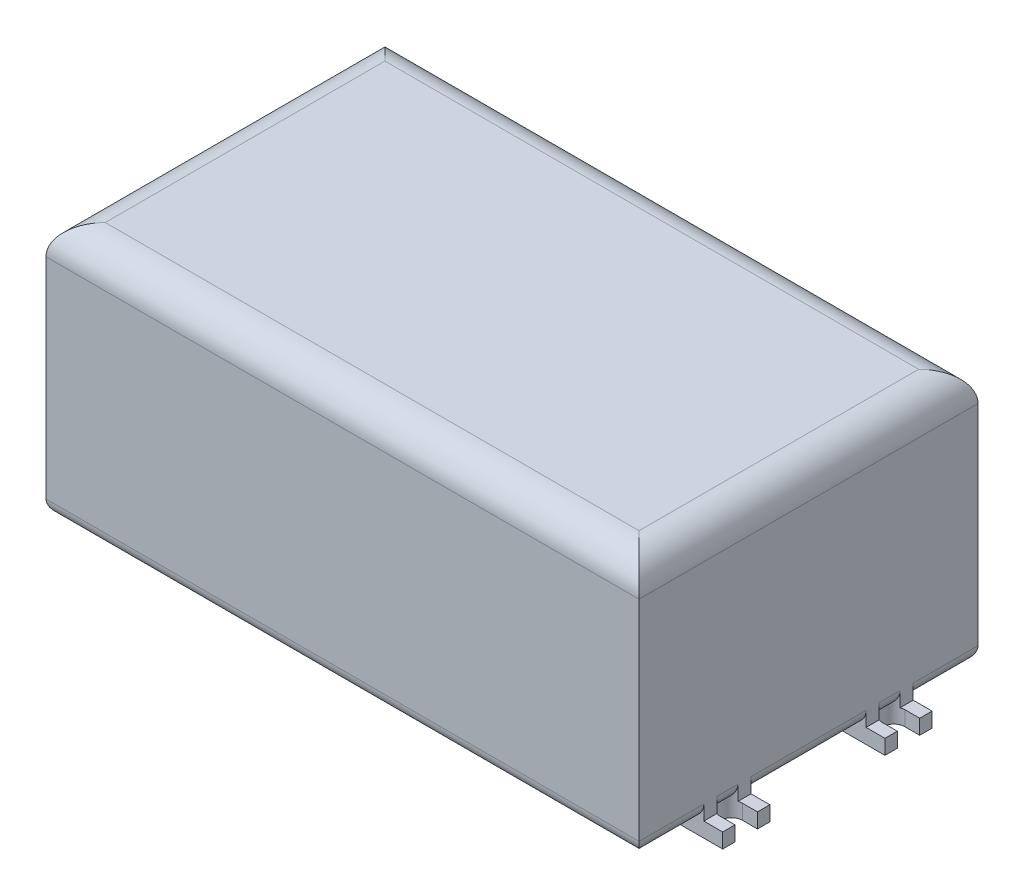
SolidWorks part; units mm, degrees
material "Custom Plastic"
ref_plane "Front Plane" through (0, 0, 0) normal (0, 0, 1) x (1, 0, 0)
ref_plane "Top Plane" through (0, 0, 0) normal (0, 1, 0) x (1, 0, 0)
ref_plane "Right Plane" through (0, 0, 0) normal (1, 0, 0) x (0, 0, -1)
sketch "Sketch1" plane through (0, 0, 0) normal (0, 1, 0) x (1, 0, 0)
  line L0 (106.36, 39.1183) -> (-106.36, 39.1183)
  line L1 (-106.36, 39.1183) -> (-106.36, 34.9483)
  line L2 (-106.36, 34.9483) -> (-101.36, 34.9483)
  line L5 (-106.36, 27.3883) -> (-101.36, 27.3883)
  line L6 (-106.36, 23.2183) -> (-106.36, 27.3883)
  line L8 (106.36, 23.2183) -> (106.36, 27.3883)
  line L9 (106.36, 27.3883) -> (101.36, 27.3883)
  line L10 (106.36, 34.9483) -> (101.36, 34.9483)
  line L11 (106.36, 39.1183) -> (106.36, 34.9483)
  line L12 (-8.6573, 23.2183) -> (-106.36, 23.2183)
  line L14 (8.6573, -15.5917) -> (8.6573, 23.2183)
  line L16 (-8.6573, -15.5917) -> (-8.6573, 23.2183)
  line L17 (8.6573, 23.2183) -> (106.36, 23.2183)
  line L18 (106.36, -15.5917) -> (8.6573, -15.5917)
  line L19 (106.36, -15.5917) -> (106.36, -19.7617)
  line L20 (106.36, -19.7617) -> (101.36, -19.7617)
  line L21 (106.36, -27.3217) -> (101.36, -27.3217)
  line L22 (106.36, -31.4917) -> (106.36, -27.3217)
  line L23 (106.36, -31.4917) -> (-106.36, -31.4917)
  line L24 (-106.36, -31.4917) -> (-106.36, -27.3217)
  line L25 (-106.36, -27.3217) -> (-101.36, -27.3217)
  line L26 (-106.36, -19.7617) -> (-101.36, -19.7617)
  line L27 (-106.36, -15.5917) -> (-106.36, -19.7617)
  line L29 (-8.6573, -15.5917) -> (-106.36, -15.5917)
  arc A0 (-101.36, 34.9483) -> (-101.36, 27.3883) centre (-101.36, 31.1683) cw
  arc A1 (101.36, 34.9483) -> (101.36, 27.3883) centre (101.36, 31.1683) ccw
  arc A2 (101.36, -27.3217) -> (101.36, -19.7617) centre (101.36, -23.5417) cw
  arc A3 (-101.36, -27.3217) -> (-101.36, -19.7617) centre (-101.36, -23.5417) ccw
  point P5 (0, 6.2533)
  dimension "D4" = 4.17
  dimension "D6" = 3.78
  dimension "D8" = 3.78
  dimension "D3" = 3.78
  dimension "D9" = 3.78
  dimension "D1" = 212.72
  dimension "D2" = 4.17
  dimension "D5" = 38.81
  dimension "D7" = 4.17
  dimension "D10" = 4.17
extrude "Boss-Extrude1" add sketch "Sketch1" along normal mid plane 5
sketch "Sketch2" plane through (0, 2.5, 0) normal (0, 1, 0) x (1, 0, 0)
  line L0 (-8.6573, 3.8133) -> (8.6573, 3.8133)
  line L1 (-8.6573, 23.2183) -> (-8.6573, -15.5917) construction
  line L2 (8.6573, -15.5917) -> (8.6573, 23.2183) construction
  line L4 (-100, -53.3367) -> (100, -53.3367)
  line L5 (-100, -53.3367) -> (-100, 60.9633)
  line L6 (-100, 60.9633) -> (100, 60.9633)
  line L7 (100, -53.3367) -> (100, 60.9633)
  line L8 (-100, -53.3367) -> (100, 60.9633) construction
  line L9 (-100, 60.9633) -> (100, -53.3367) construction
  point P6 (0, 3.8133)
  dimension "D1" = 114.3
  dimension "D2" = 200
extrude "Boss-Extrude3" add sketch "Sketch2" along normal blind 85.725 contours L5 L6 L7 L4
sketch "Sketch3" plane through (-100, 0, 0) normal (-1, 0, 0) x (0, 0, 1)
  line L0 (-60.9633, 45.3625) -> (53.3367, 45.3625)
  line L1 (-60.9633, 88.225) -> (-60.9633, 2.5) construction
  line L2 (53.3367, 88.225) -> (53.3367, 2.5) construction
  line L3 (-3.8133, 88.225) -> (-3.8133, 2.5)
  line L4 (53.3367, 88.225) -> (-60.9633, 88.225) construction
  line L5 (-23.2183, 2.5) -> (15.5917, 2.5) construction
  line L6 (-16.2033, 41.9216) -> (6.1167, 41.9216)
  line L7 (-36.2033, 35.3625) -> (-16.2033, 35.3625)
  line L8 (-36.2033, 35.3625) -> (-36.2033, 55.3625)
  line L9 (-36.2033, 55.3625) -> (-16.2033, 55.3625)
  line L11 (-36.2033, 35.3625) -> (-16.2033, 55.3625) construction
  line L12 (-36.2033, 55.3625) -> (-16.2033, 35.3625) construction
  line L13 (6.1167, 35.3625) -> (26.1167, 35.3625)
  line L15 (6.1167, 55.3625) -> (26.1167, 55.3625)
  line L16 (26.1167, 35.3625) -> (26.1167, 55.3625)
  line L17 (6.1167, 35.3625) -> (26.1167, 55.3625) construction
  line L18 (6.1167, 55.3625) -> (26.1167, 35.3625) construction
  line L19 (-16.2033, 41.9216) -> (-16.2033, 35.3625)
  line L20 (6.1167, 41.9216) -> (6.1167, 35.3625)
  line L21 (6.1167, 48.3286) -> (-16.2033, 48.3286)
  line L22 (-16.2033, 48.3286) -> (-16.2033, 55.3625)
  line L23 (6.1167, 55.3625) -> (6.1167, 48.3286)
  point P12 (-26.2033, 45.3625)
  point P17 (16.1167, 45.3625)
  dimension "D1" = 20
  dimension "D2" = 20
  dimension "D3" = 20
  dimension "D4" = 20
  dimension "D6" = 24.76
extrude "Boss-Extrude5" add sketch "Sketch3" along normal blind 20 contours L8 L9 L22 L21 L23 L15 L16 L13 L20 L6 L19 L7
fillet "Fillet1" radius 5 16 edges at (-97.58, 2.5, 23.5417) (97.58, 2.5, 23.5417) (97.58, 2.5, -31.1683) (-97.58, 2.5, -31.1683) (-100, 2.5, 23.5417) (-100, 2.5, 42.4142) (-100, 2.5, -50.0408) (0, 2.5, -60.9633) (-100, 2.5, -31.1683) (-100, 2.5, -3.8133) (0, 2.5, 53.3367) (100, 2.5, 42.4142) (100, 2.5, 23.5417) (100, 2.5, -3.8133) (100, 2.5, -31.1683) (100, 2.5, -50.0408)
fillet "Fillet2" radius 10 4 edges at (-100, 88.225, -3.8133) (0, 88.225, 53.3367) (100, 88.225, -3.8133) (0, 88.225, -60.9633)
